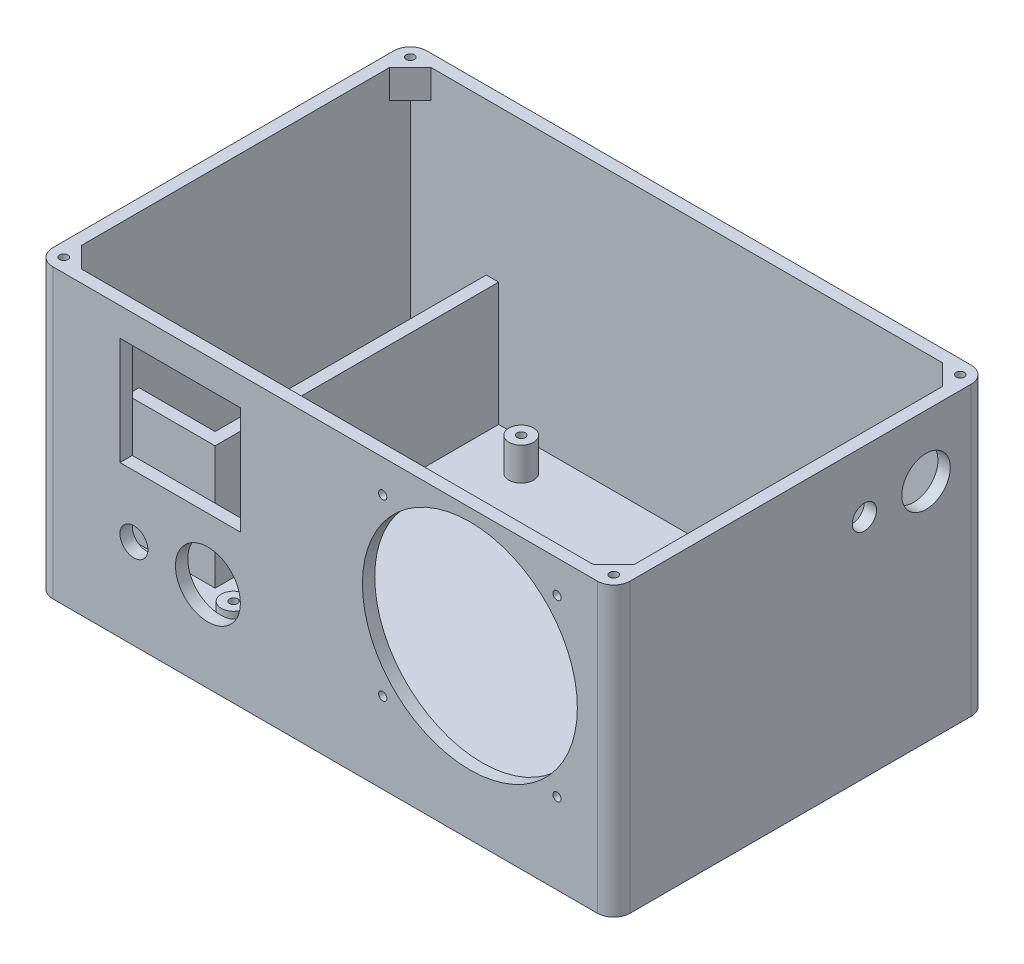
SolidWorks part; units mm, degrees
ref_plane "Front Plane" through (0, 0, 0) normal (0, 0, 1) x (1, 0, 0)
ref_plane "Top Plane" through (0, 0, 0) normal (0, 1, 0) x (1, 0, 0)
ref_plane "Right Plane" through (0, 0, 0) normal (1, 0, 0) x (0, 0, -1)
sketch "Sketch1" plane through (0, 0, 0) normal (0, 1, 0) x (1, 0, 0)
  line L7 (-79.5, -42.5) -> (55, -42.5)
  line L8 (-79.5, -42.5) -> (-79.5, 42.5)
  line L9 (-79.5, 42.5) -> (55, 42.5)
  line L10 (55, -42.5) -> (55, 42.5)
  line L11 (-79.5, -42.5) -> (55, 42.5) construction
  point P0 (0, 0)
  point P6 (-12.25, 0)
  dimension "D1" = 134.5
  dimension "D2" = 42.5
  dimension "D3" = 85
  dimension "D4" = 55
extrude "Boss-Extrude1" add sketch "Sketch1" along normal blind 3
sketch "Sketch2" plane through (0, 0, 0) normal (0, 1, 0) x (1, 0, 0)
  line L0 (55, -42.5) -> (55, 42.5) construction
  line L1 (-82.5, -45.5) -> (58, -45.5)
  line L2 (-82.5, -45.5) -> (-82.5, 45.5)
  line L3 (-82.5, 45.5) -> (58, 45.5)
  line L4 (58, -45.5) -> (58, 45.5)
  line L5 (-82.5, -45.5) -> (58, 45.5) construction
  line L6 (-82.5, 45.5) -> (58, -45.5) construction
  line L7 (-79.5, 42.5) -> (-79.5, -42.5) construction
  line L8 (55, 42.5) -> (-79.5, 42.5) construction
  line L9 (-79.5, -42.5) -> (55, -42.5) construction
  line L11 (-79.5, -42.5) -> (55, -42.5)
  line L12 (-79.5, -42.5) -> (-79.5, 42.5)
  line L13 (-79.5, 42.5) -> (55, 42.5)
  line L14 (55, -42.5) -> (55, 42.5)
  line L15 (-79.5, -42.5) -> (55, 42.5) construction
  line L16 (-79.5, 42.5) -> (55, -42.5) construction
  point P0 (-12.25, 0)
  point P13 (-12.25, 0)
  dimension "D1" = 3
  dimension "D2" = 3
  dimension "D3" = 3
  dimension "D4" = 3
extrude "Boss-Extrude2" add sketch "Sketch2" along normal blind 70
sketch "Sketch3" plane through (0, 3, 0) normal (0, 1, 0) x (1, 0, 0)
  line L1 (-50, -40) -> (50, -40)
  line L2 (-50, -40) -> (-50, 40)
  line L3 (-50, 40) -> (50, 40)
  line L4 (50, -40) -> (50, 40)
  line L5 (-50, -40) -> (50, 40) construction
  line L6 (-50, 40) -> (50, -40) construction
  point P0 (0, 0)
  dimension "D1" = 80
  dimension "D2" = 100
extrude "Boss-Extrude3" add sketch "Sketch3" along normal blind 5 from offset 5 separate body
sketch "Sketch4" plane through (0, 0, -42.5) normal (0, 0, 1) x (1, 0, 0)
  line L5 (55, 3) -> (-79.5, 3) construction
  line L6 (-50, 13) -> (-50, 8) construction
  circle A0 centre (-70.25, 12.25) radius 9.25
  circle A1 centre (-70.25, 30.75) radius 9.25
  line M3 (55, 70) -> (-79.5, 70)
  dimension "D1" = 18.5
  dimension "D2" = 20.25
extrude "Boss-Extrude4" [suppressed] add sketch "Sketch4" along normal blind 33 from surface separate body contours A0 M3 | A1
mirror "Mirror2" [suppressed] about plane through (0, 0, 0) normal (0, 0, 1)
sketch "Sketch5" plane through (0, 3, 0) normal (0, 1, 0) x (1, 0, 0)
  line L1 (-58, -23.5) -> (-61, -23.5)
  line L2 (-58, -23.5) -> (-58, 42.5)
  line L3 (-58, 42.5) -> (-61, 42.5)
  line L4 (-61, -23.5) -> (-61, 42.5)
  line L5 (-58, -23.5) -> (-61, 42.5) construction
  line L6 (-58, 42.5) -> (-61, -23.5) construction
  line L7 (55, 42.5) -> (-79.5, 42.5) construction
  line L8 (-58, -23.5) -> (-58, -26.5)
  line L9 (-58, -26.5) -> (-79.5, -26.5)
  line L10 (-79.5, 42.5) -> (-79.5, -42.5) construction
  line L11 (-79.5, -26.5) -> (-79.5, -23.5)
  line L12 (-79.5, 42.5) -> (-79.5, -42.5) construction
  line L13 (-79.5, -23.5) -> (-61, -23.5)
  point P0 (-59.5, 9.5)
  line M4 (55, 42.5) -> (-79.5, 42.5)
  line M14 (-79.5, 42.5) -> (-79.5, -42.5)
  dimension "D1" = 3
  dimension "D2" = 66
  dimension "D3" = 8
  dimension "D4" = 3
extrude "Boss-Extrude5" add sketch "Sketch5" along normal blind 30 contours L13 L9 L8 L1 M14 | L4 L1 L2 M4 region at (-68.75, 3, 25) region at (-59.5, 3, -9.5)
sketch "Sketch6" plane through (0, 3, 0) normal (0, 1, 0) x (1, 0, 0)
  line L0 (-50, -40) -> (50, -40) construction
  line L1 (-50, 40) -> (-50, -40) construction
  circle A1 centre (-45, -35) radius 3
  circle A2 centre (-45, -35) radius 1
  dimension "D1" = 2
  dimension "D2" = 6
  dimension "D3" = 5
  dimension "D4" = 5
extrude "Boss-Extrude6" add sketch "Sketch6" along normal up to body separate body
sketch "Sketch7" plane through (0, 13, 0) normal (0, 1, 0) x (1, 0, 0)
  line L0 (-50, 40) -> (-50, -40) construction
  line L1 (50, -40) -> (-50, -40)
  line L2 (50, -40) -> (50, 40)
  line L3 (50, 40) -> (-50, 40)
  line L4 (-50, -40) -> (-50, 40)
  line L5 (50, -40) -> (-50, 40) construction
  line L6 (50, 40) -> (-50, -40) construction
  point P0 (0, 0)
  dimension "D1" = 80
extrude "Cut-Extrude2" cut sketch "Sketch7" against normal blind 10 from surface starting at face at (0, 13, 0)
extrude "Boss-Extrude7" add sketch "Sketch6<2>" along normal blind 8
sketch "Sketch6<2>" plane through (0, 3, 0) normal (0, 1, 0) x (1, 0, 0) same geometry as "Sketch6"
mirror "Mirror3" about plane through (0, 0, 0) normal (0, 0, 1) of "Boss-Extrude7"
mirror "Mirror4" about plane through (0, 0, 0) normal (1, 0, 0) of "Boss-Extrude7", "Mirror3"
sketch "Sketch9" plane through (0, 0, 45.5) normal (0, 0, 1) x (1, 0, 0)
  line L1 (-3.15, 67) -> (49.15, 67)
  line L2 (-3.15, 67) -> (-3.15, 14.7)
  line L3 (-3.15, 14.7) -> (49.15, 14.7)
  line L4 (49.15, 67) -> (49.15, 14.7)
  line L5 (-3.15, 67) -> (49.15, 14.7) construction
  line L6 (-3.15, 14.7) -> (49.15, 67) construction
  line L8 (-82.5, 70) -> (58, 70) construction
  line L9 (58, 70) -> (58, 0) construction
  line L10 (-82.5, 70) -> (-82.5, 0) construction
  line L11 (-62.15, 63.1) -> (-32.85, 63.1)
  line L12 (-62.15, 63.1) -> (-62.15, 36.9)
  line L13 (-62.15, 36.9) -> (-32.85, 36.9)
  line L14 (-32.85, 63.1) -> (-32.85, 36.9)
  line L15 (-62.15, 63.1) -> (-32.85, 36.9) construction
  line L16 (-62.15, 36.9) -> (-32.85, 63.1) construction
  line L17 (-47.5, 36.9) -> (-47.5, 0) construction
  line L18 (-82.5, 0) -> (58, 0) construction
  circle A0 centre (23, 40.85) radius 26.15
  circle A1 centre (1.7868, 62.0632) radius 1
  circle A2 centre (44.2132, 62.0632) radius 1
  circle A3 centre (44.2132, 19.6368) radius 1
  circle A4 centre (1.7868, 19.6368) radius 1
  circle A5 centre (-58.75, 21.9) radius 3.4
  circle A6 centre (-40.75, 21.9) radius 7.9
  point P20 (-47.5, 50)
  dimension "D1" = 52.3
  dimension "D3" = 2
  dimension "D8" = 6.8
  dimension "D9" = 15.8
  dimension "D2" = 3
  dimension "D4" = 60
  dimension "D5" = 35
  dimension "D6" = 26.2
  dimension "D7" = 29.3
  dimension "D10" = 35
  dimension "D11" = 50
  dimension "D12" = 15
extrude "Cut-Extrude3" cut sketch "Sketch9" against normal up to surface (3 mm away) contours A0 | A4 | A3 | A2 | A1 | A5 | A6 | L14 L11 L12 L13 region at (23, 40.85, 45.5) region at (-47.5, 50, 45.5) region at (1.7868, 62.0632, 45.5) region at (44.2132, 62.0632, 45.5) region at (44.2132, 19.6368, 45.5) region at (1.7868, 19.6368, 45.5) region at (-58.75, 21.9, 45.5) region at (-40.75, 21.9, 45.5) up to face at (-12.25, 36.5, 42.5)
sketch "Sketch10" plane through (58, 0, 0) normal (1, 0, 0) x (0, 0, -1)
  line L0 (-45.5, 70) -> (45.5, 70) construction
  line L1 (45.5, 70) -> (45.5, 0) construction
  circle A0 centre (15.5, 55) radius 2.95
  circle A1 centre (30.5, 55) radius 5.9
  dimension "D1" = 5.9
  dimension "D2" = 11.8
  dimension "D3" = 15
  dimension "D4" = 15
  dimension "D5" = 15
extrude "Cut-Extrude4" cut sketch "Sketch10" against normal up to surface (3 mm away) up to face at (55, 36.5, 0)
sketch "Sketch11" plane through (0, 70, 0) normal (0, 1, 0) x (1, 0, 0)
  line L0 (50, 37.5) -> (58, 45.5) construction
  line L1 (-79.5, 42.5) -> (-74.5, 42.5)
  line L2 (-79.5, 42.5) -> (-79.5, 37.5)
  line L3 (-79.5, 37.5) -> (-74.5, 37.5)
  line L4 (-74.5, 42.5) -> (-74.5, 37.5)
  line L5 (55, 42.5) -> (50, 42.5)
  line L6 (55, 42.5) -> (55, 37.5)
  line L7 (55, 37.5) -> (50, 37.5)
  line L8 (50, 42.5) -> (50, 37.5)
  line L9 (55, -42.5) -> (50, -42.5)
  line L10 (55, -42.5) -> (55, -37.5)
  line L11 (55, -37.5) -> (50, -37.5)
  line L12 (50, -42.5) -> (50, -37.5)
  line L13 (-79.5, -42.5) -> (-74.5, -42.5)
  line L14 (-79.5, -42.5) -> (-79.5, -37.5)
  line L15 (-79.5, -37.5) -> (-74.5, -37.5)
  line L16 (-74.5, -42.5) -> (-74.5, -37.5)
  line L17 (-79.5, -37.5) -> (-74.5, -42.5)
  line L18 (50, -42.5) -> (55, -37.5)
  line L19 (55, 37.5) -> (50, 42.5)
  line L20 (-79.5, 37.5) -> (-74.5, 42.5)
  line M6 (55, 42.5) -> (55, -42.5)
  line M7 (55, -42.5) -> (-79.5, -42.5)
  line M8 (-79.5, -42.5) -> (-79.5, 42.5)
  line M9 (-79.5, 42.5) -> (55, 42.5)
  dimension "D1" = 5
extrude "Boss-Extrude8" add sketch "Sketch11" against normal blind 7 contours L17 M8 M7 | L20 M8 M9 | L19 L0 M9 | L0 L19 M6 | L18 M7 M6 region at (52.5, 70, -41.6667) region at (54.1667, 70, -40) region at (53.3333, 70, 40.8333) region at (-77.8333, 70, -40.8333) region at (-77.8333, 70, 40.8333)
fillet "Fillet1" radius 4 4 edges at (-82.5, 35, -45.5) (58, 35, -45.5) (58, 35, 45.5) (-82.5, 35, 45.5)
sketch "Sketch13" plane through (0, 70, 0) normal (0, 1, 0) x (1, 0, 0)
  line L0 (-81.3284, 44.3284) -> (-77, 40)
  line L2 (-79.5, 37.5) -> (-74.5, 42.5) construction
  line L4 (-77, 40) -> (-77, -40)
  line L5 (-79.5, -37.5) -> (-74.5, -42.5) construction
  line L6 (-77, -40) -> (-81.3284, -44.3284)
  line L8 (-81.3284, -44.3284) -> (56.8284, -44.3284)
  line L10 (56.8284, -44.3284) -> (52.5, -40)
  line L14 (50, -42.5) -> (55, -37.5) construction
  line L15 (52.5, -40) -> (52.5, 40)
  line L16 (55, 37.5) -> (50, 42.5) construction
  line L17 (52.5, 40) -> (56.8284, 44.3284)
  arc A4 (-78.5, 45.5) -> (-82.5, 41.5) centre (-78.5, 41.5) ccw construction
  arc A5 (-82.5, -41.5) -> (-78.5, -45.5) centre (-78.5, -41.5) ccw construction
  arc A6 (54, -45.5) -> (58, -41.5) centre (54, -41.5) ccw construction
  arc A7 (58, 41.5) -> (54, 45.5) centre (54, 41.5) ccw construction
  circle A8 centre (-79.1642, 42.1642) radius 1
  circle A10 centre (54.6642, 42.1642) radius 1
  circle A11 centre (54.6642, -42.1642) radius 1
  circle A12 centre (-79.1642, -42.1642) radius 1
  dimension "D1" = 2
extrude "Cut-Extrude6" cut sketch "Sketch13" against normal blind 5 contours L17 A10 | L17 A10 | L10 A11 | L6 A12 | L6 A12 | L0 A8 | L0 A8 | A11 region at (-78.8641, 70, -42.4643) region at (54.3641, 70, -42.4643) region at (54.9643, 70, -41.8641) region at (54.9643, 70, 41.8641) region at (-78.8641, 70, 42.4643) region at (-79.4643, 70, 41.8641) region at (-79.4643, 70, -41.8641)
